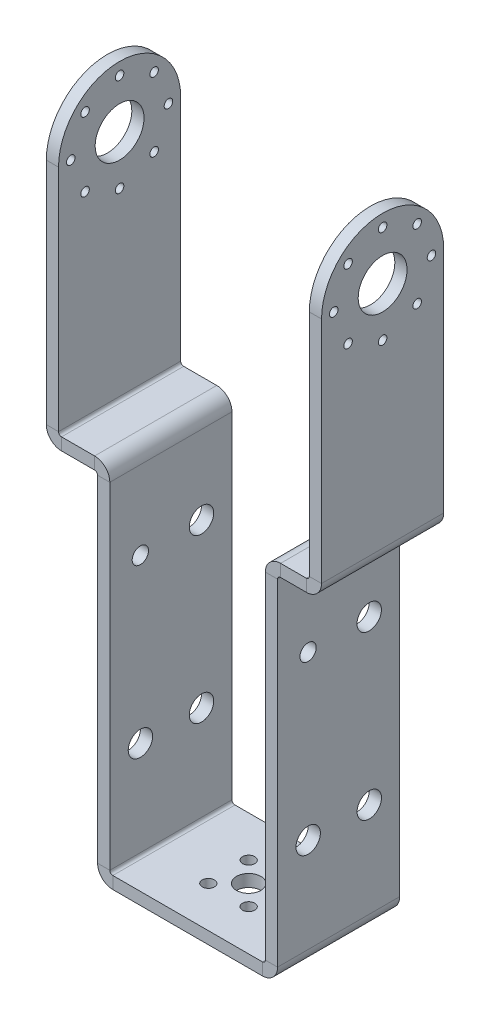
SolidWorks part; units mm, degrees
note: The reader was unsure of these and kept them because the rebuilt part matched: flange length of "边线-法兰1", "边线-法兰2", "边线-法兰3", "边线-法兰4", "边线-法兰5", "边线-法兰6".
material "1060 合金"
ref_plane "前视基准面" through (0, 0, 0) normal (0, 0, 1) x (1, 0, 0)
ref_plane "上视基准面" through (0, 0, 0) normal (0, 1, 0) x (1, 0, 0)
ref_plane "右视基准面" through (0, 0, 0) normal (1, 0, 0) x (0, 0, -1)
sketch "草图1" plane through (0, 0, 0) normal (0, 1, 0) x (1, 0, 0)
  line L0 (-55.6, 31.2134) -> (-11.4, 31.2134)
  line L1 (-55.6, 31.2134) -> (-55.6, 1.2134)
  line L2 (-11.4, 31.2134) -> (-11.4, 1.2134)
  line L3 (-55.6, 1.2134) -> (-11.4, 1.2134)
  dimension "D1" = 44.2
  dimension "D2" = 30
base flange "基体-法兰1" sketch "草图1" thickness 3 reverse thickness direction no parameters "D1"=0.7366
edge flange "边线-法兰1" sketch "草图4" flange angle 90 flange length 90 flange position material inside bend radius 0.7366 thickness 3 relief rectangular parameters "D6"=10
sketch "草图4" plane through (-55.6, 0, 0) normal (-1, 0, 0) x (0, 0, 1)
  line L0 (-31.2134, 0) -> (-1.2134, 0) construction
  line L1 (-31.2134, 0) -> (-1.2134, 0)
  line L2 (-31.2134, 0) -> (-31.2134, 87)
  line L3 (-31.2134, 87) -> (-1.2134, 87)
  line L4 (-1.2134, 87) -> (-1.2134, 0)
bend "边线折弯1" bend radius 0.7366 bend angle 90 parameters "D5"=1
edge flange "边线-法兰2" sketch "草图7" flange angle 90 flange length 90 flange position material inside bend radius 0.7366 thickness 3 relief rectangular parameters "D6"=10
sketch "草图7" plane through (-11.4, 0, 0) normal (1, 0, 0) x (0, 0, -1)
  line L0 (1.2134, 0) -> (31.2134, 0) construction
  line L1 (1.2134, 0) -> (31.2134, 0)
  line L2 (1.2134, 0) -> (1.2134, 87)
  line L3 (1.2134, 87) -> (31.2134, 87)
  line L4 (31.2134, 87) -> (31.2134, 0)
bend "边线折弯2" bend radius 0.7366 bend angle 90 parameters "D5"=2
edge flange "边线-法兰3" sketch "草图10" flange angle 90 flange length 13.8 flange position material inside bend radius 0.7366 thickness 3 relief rectangular parameters "D6"=10
sketch "草图10" plane through (-11.4, 87, 0) normal (0, 1, 0) x (0, 0, 1)
  line L0 (-31.2134, 0) -> (-1.2134, 0) construction
  line L1 (-31.2134, 0) -> (-1.2134, 0)
  line L2 (-31.2134, 0) -> (-31.2134, 10.8)
  line L3 (-31.2134, 10.8) -> (-1.2134, 10.8)
  line L4 (-1.2134, 10.8) -> (-1.2134, 0)
bend "边线折弯3" bend radius 0.7366 bend angle 90 parameters "D5"=3
edge flange "边线-法兰4" sketch "草图13" flange angle 90 flange length 15.6 flange position material inside bend radius 0.7366 thickness 3 relief rectangular parameters "D6"=10
sketch "草图13" plane through (-55.6, 87, 0) normal (0, 1, 0) x (0, 0, -1)
  line L2 (1.2134, 0) -> (1.2134, 12.6)
  line L3 (1.2134, 12.6) -> (31.2134, 12.6)
  line L4 (31.2134, 12.6) -> (31.2134, 0)
  line L7 (1.2134, 0) -> (31.2134, 0) construction
  line L8 (1.2134, 0) -> (31.2134, 0)
bend "边线折弯4" bend radius 0.7366 bend angle 90 parameters "D5"=4
edge flange "边线-法兰5" sketch "草图16" flange angle 90 flange length 75 flange position material inside bend radius 0.7366 thickness 3 relief rectangular parameters "D6"=10
sketch "草图16" plane through (-68.2, 87, 0) normal (-1, 0, 0) x (0, 0, 1)
  line L2 (-31.2134, 0) -> (-31.2134, 72)
  line L3 (-31.2134, 72) -> (-1.2134, 72)
  line L4 (-1.2134, 72) -> (-1.2134, 0)
  line L7 (-31.2134, 0) -> (-1.2134, 0) construction
  line L8 (-31.2134, 0) -> (-1.2134, 0)
bend "边线折弯5" bend radius 0.7366 bend angle 90 parameters "D5"=5
edge flange "边线-法兰6" sketch "草图19" flange angle 90 flange length 75 flange position material inside bend radius 0.7366 thickness 3 relief rectangular parameters "D6"=10
sketch "草图19" plane through (-0.6, 87, 0) normal (1, 0, 0) x (0, 0, -1)
  line L0 (1.2134, 0) -> (31.2134, 0) construction
  line L1 (1.2134, 0) -> (31.2134, 0)
  line L2 (1.2134, 0) -> (1.2134, 72)
  line L3 (1.2134, 72) -> (31.2134, 72)
  line L4 (31.2134, 72) -> (31.2134, 0)
bend "边线折弯6" bend radius 0.7366 bend angle 90 parameters "D5"=6
sketch "草图20" plane through (-0.6, 0, 0) normal (1, 0, 0) x (0, 0, -1)
  line L0 (16.2134, 159) -> (16.2134, 144) construction
  line L1 (31.2134, 159) -> (1.2134, 159) construction
  line L2 (31.2134, 144) -> (31.2134, 159)
  line L3 (31.2134, 159) -> (1.2134, 159)
  line L4 (1.2134, 159) -> (1.2134, 144)
  circle A0 centre (16.2134, 144) radius 15
  circle A1 centre (16.2134, 144) radius 6
  circle A2 centre (16.2134, 156) radius 1.05
  circle A3 centre (24.6987, 152.4853) radius 1.05
  circle A4 centre (28.2134, 144) radius 1.05
  circle A5 centre (24.6987, 135.5147) radius 1.05
  circle A6 centre (16.2134, 132) radius 1.05
  circle A7 centre (7.7281, 135.5147) radius 1.05
  circle A8 centre (4.2134, 144) radius 1.05
  circle A9 centre (7.7281, 152.4853) radius 1.05
  dimension "D1" = 12
  dimension "D2" = 8
extrude "切除-拉伸1" cut sketch "草图20" against normal blind 100
sketch "草图21" plane through (0, -3, 0) normal (0, -1, 0) x (1, 0, 0)
  line L0 (-33.5, -1.2134) -> (-33.5, -31.2134) construction
  line L1 (-51.8634, -1.2134) -> (-15.1366, -1.2134) construction
  line L2 (-15.1366, -31.2134) -> (-51.8634, -31.2134) construction
  line L3 (-33.5, -16.2134) -> (-28.5503, -11.2637) construction
  circle A0 centre (-33.5, -16.2134) radius 3
  circle A1 centre (-28.5503, -11.2637) radius 1.5
  circle A2 centre (-28.5503, -21.1632) radius 1.5
  circle A3 centre (-38.4497, -21.1632) radius 1.5
  circle A4 centre (-38.4497, -11.2637) radius 1.5
  dimension "D1" = 4
extrude "切除-拉伸2" cut sketch "草图21" against normal blind 10 normal cut yes
sketch "草图22" plane through (-11.4, 0, 0) normal (1, 0, 0) x (0, 0, -1)
  line L0 (23.7391, 24.0038) -> (8.7285, 24.0038)
  line L1 (23.7187, 64.0038) -> (8.7081, 63.9962)
  line L2 (1.2134, 83.2634) -> (31.2134, 83.2634) construction
  line L4 (31.2134, 84) -> (1.2134, 84) construction
  line L6 (31.2134, 84) -> (1.2134, 84)
  line L7 (23.7187, 64.0038) -> (23.7391, 24.0038)
  line L8 (8.7081, 63.9962) -> (8.7285, 24.0038)
  line L10 (16.2134, 19.8886) -> (16.2134, 64) construction
  circle A0 centre (23.7187, 64.0038) radius 3
  circle A1 centre (8.7285, 24.0038) radius 3
  circle A2 centre (23.7391, 24.0038) radius 3
  circle A3 centre (8.7081, 63.9962) radius 2
  point P3 (16.2134, 83.2634)
  dimension "D1" = 0.029
  dimension "D2" = 20
  dimension "D3" = 40
extrude "切除-拉伸3" cut sketch "草图22" against normal blind 66 contours L1 A3 L8 | L8 A3 L1 | A2 | A1 | A0 normal cut yes
sketch "折弯-线1" plane through (0, 0, 0) normal (0, 1, 0) x (1, 0, 0)
sketch "边界框1" plane through (0, 0, 0) normal (0, 1, 0) x (1, 0, 0)
sheet metal parameters "钣金6" thickness 3 parameters "D1"=0.7366
flat pattern "平板型式6" [suppressed]
sketch "折弯-线2" plane through (0, 0, 0) normal (0, 1, 0) x (1, 0, 0)
sketch "边界框2" [suppressed] plane through (0, 0, 0) normal (0, 1, 0) x (1, 0, 0)
sheet metal parameters "钣金7" thickness 3 parameters "D1"=0.7366
flat pattern "平板型式6" [suppressed]
sketch "折弯-线2" plane through (0, 0, 0) normal (0, 1, 0) x (1, 0, 0)
sketch "边界框2" [suppressed] plane through (0, 0, 0) normal (0, 1, 0) x (1, 0, 0)
bend of the flat pattern "展平-<边线折弯1>1"
sheet metal parameters "钣金8" thickness 3 parameters "D1"=0.7366
flat pattern "平板型式6" [suppressed]
sketch "折弯-线2" plane through (0, 0, 0) normal (0, 1, 0) x (1, 0, 0)
sketch "边界框2" [suppressed] plane through (0, 0, 0) normal (0, 1, 0) x (1, 0, 0)
bend of the flat pattern "展平-<边线折弯1>1"
bend of the flat pattern "展平-<边线折弯2>1"
sheet metal parameters "钣金9" thickness 3 parameters "D1"=0.7366
flat pattern "平板型式6" [suppressed]
sketch "折弯-线2" plane through (0, 0, 0) normal (0, 1, 0) x (1, 0, 0)
sketch "边界框2" [suppressed] plane through (0, 0, 0) normal (0, 1, 0) x (1, 0, 0)
bend of the flat pattern "展平-<边线折弯1>1"
bend of the flat pattern "展平-<边线折弯2>1"
bend of the flat pattern "展平-<边线折弯3>1"
sheet metal parameters "钣金10" thickness 3 parameters "D1"=0.7366
flat pattern "平板型式6" [suppressed]
sketch "折弯-线2" plane through (0, 0, 0) normal (0, 1, 0) x (1, 0, 0)
sketch "边界框2" [suppressed] plane through (0, 0, 0) normal (0, 1, 0) x (1, 0, 0)
bend of the flat pattern "展平-<边线折弯1>1"
bend of the flat pattern "展平-<边线折弯2>1"
bend of the flat pattern "展平-<边线折弯3>1"
bend of the flat pattern "展平-<边线折弯4>1"
sheet metal parameters "钣金11" thickness 3 parameters "D1"=0.7366
flat pattern "平板型式6" [suppressed]
sketch "折弯-线2" plane through (0, 0, 0) normal (0, 1, 0) x (1, 0, 0)
sketch "边界框2" [suppressed] plane through (0, 0, 0) normal (0, 1, 0) x (1, 0, 0)
bend of the flat pattern "展平-<边线折弯1>1"
bend of the flat pattern "展平-<边线折弯2>1"
bend of the flat pattern "展平-<边线折弯3>1"
bend of the flat pattern "展平-<边线折弯4>1"
bend of the flat pattern "展平-<边线折弯5>1"
sheet metal parameters "钣金12" thickness 3 parameters "D1"=0.7366
flat pattern "平板型式6" [suppressed]
sketch "折弯-线2" plane through (0, 0, 0) normal (0, 1, 0) x (1, 0, 0)
sketch "边界框2" [suppressed] plane through (0, 0, 0) normal (0, 1, 0) x (1, 0, 0)
bend of the flat pattern "展平-<边线折弯1>1"
bend of the flat pattern "展平-<边线折弯2>1"
bend of the flat pattern "展平-<边线折弯3>1"
bend of the flat pattern "展平-<边线折弯4>1"
bend of the flat pattern "展平-<边线折弯5>1"
bend of the flat pattern "展平-<边线折弯6>1"
sheet metal parameters "钣金13" thickness 3 parameters "D1"=0.7366
flat pattern "平板型式6" [suppressed]
sketch "折弯-线2" plane through (0, 0, 0) normal (0, 1, 0) x (1, 0, 0)
sketch "边界框2" [suppressed] plane through (0, 0, 0) normal (0, 1, 0) x (1, 0, 0)
bend of the flat pattern "展平-<边线折弯1>1"
bend of the flat pattern "展平-<边线折弯2>1"
bend of the flat pattern "展平-<边线折弯3>1"
bend of the flat pattern "展平-<边线折弯6>1"
bend of the flat pattern "展平-<边线折弯4>1"
bend of the flat pattern "展平-<边线折弯5>1"
sheet metal parameters "钣金14" thickness 3 parameters "D1"=0.7366
flat pattern "平板型式6" [suppressed]
sketch "折弯-线2" plane through (0, 0, 0) normal (0, 1, 0) x (1, 0, 0)
sketch "边界框2" [suppressed] plane through (0, 0, 0) normal (0, 1, 0) x (1, 0, 0)
bend of the flat pattern "展平-<边线折弯1>1"
bend of the flat pattern "展平-<边线折弯2>1"
bend of the flat pattern "展平-<边线折弯3>1"
bend of the flat pattern "展平-<边线折弯6>1"
bend of the flat pattern "展平-<边线折弯4>1"
bend of the flat pattern "展平-<边线折弯5>1"
sheet metal parameters "钣金15" thickness 3 parameters "D1"=0.7366
flat pattern "平板型式6" [suppressed]
sketch "折弯-线2" plane through (0, 0, 0) normal (0, 1, 0) x (1, 0, 0)
sketch "边界框2" [suppressed] plane through (0, 0, 0) normal (0, 1, 0) x (1, 0, 0)
bend of the flat pattern "展平-<边线折弯1>1"
bend of the flat pattern "展平-<边线折弯2>1"
bend of the flat pattern "展平-<边线折弯3>1"
bend of the flat pattern "展平-<边线折弯6>1"
bend of the flat pattern "展平-<边线折弯4>1"
bend of the flat pattern "展平-<边线折弯5>1"
